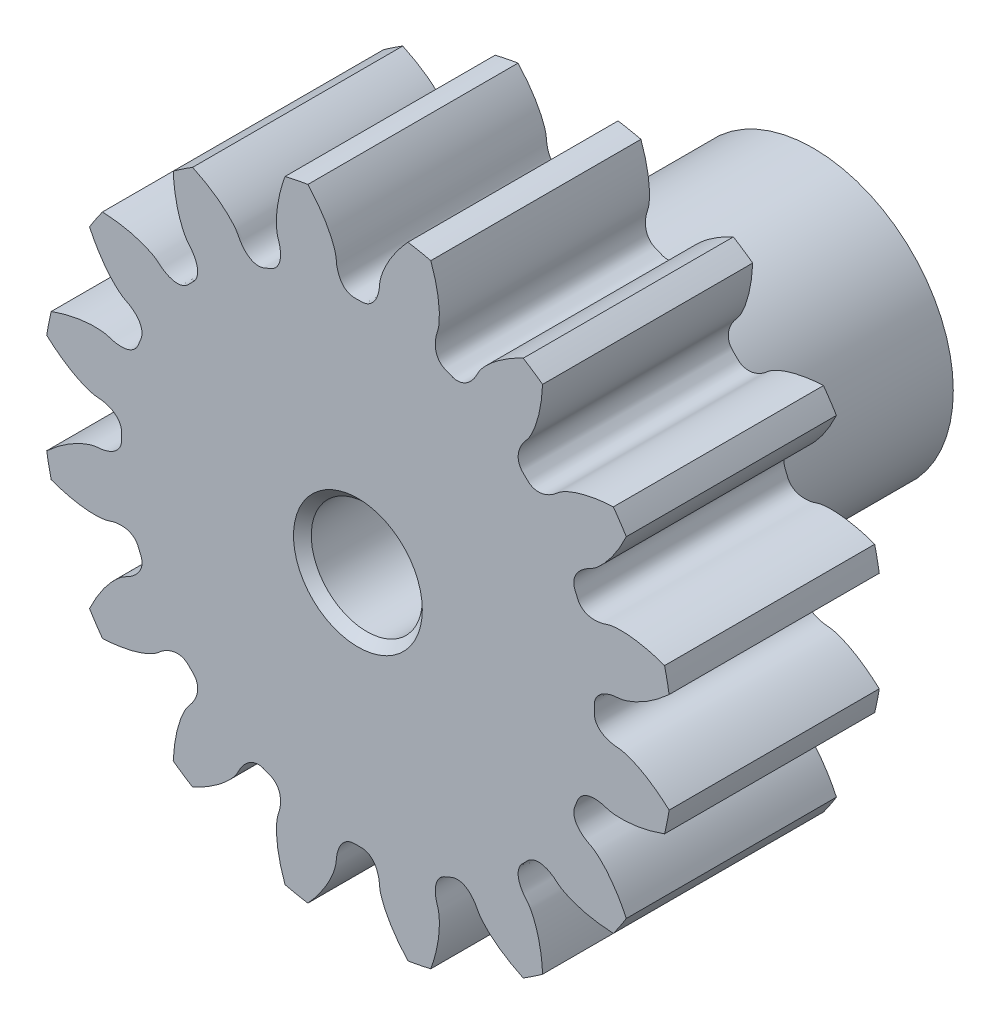
SolidWorks part; units mm, degrees
material "Plain Carbon Steel"
ref_plane "Спереди" through (0, 0, 0) normal (0, 0, 1) x (1, 0, 0)
ref_plane "Сверху" through (0, 0, 0) normal (0, 1, 0) x (1, 0, 0)
ref_plane "Справа" through (0, 0, 0) normal (1, 0, 0) x (0, 0, -1)
ref_axis "Axis1" through (0, 0, 50) along (0, 0, -1)
sketch "SketchRevolveSpur01" plane through (0, 0, 0) normal (1, 0, 0) x (0, 0, -1)
  line L0 (0, 0) -> (1, 0) construction
  line L1 (-3, 0) -> (-3, 9)
  line L2 (-3, 9) -> (3, 9)
  line L3 (3, 9) -> (3, 0)
  line L4 (3, 0) -> (-3, 0)
revolve "Spur01" add sketch "SketchRevolveSpur01" angle 360 about L0
sketch "SketchToothSpur01" plane through (0, 0, 0) normal (0, 0, 1) x (1, 0, 0)
  arc A0 (8.93, 1.469) -> (8.93, -1.469) centre (0, 0) cw
  spline S0 degree 3 poles (8.93, -1.469) (8.852, -1.3959) (8.7347, -1.2926) (8.5758, -1.1667) (8.4638, -1.0839) (8.356, -1.0096) (8.2529, -0.9435) (8.1549, -0.8853) (8.0624, -0.8344) (7.9758, -0.7905) (7.8955, -0.7531) (7.8216, -0.7216) (7.7547, -0.6957) (7.6949, -0.6749) (7.6425, -0.6585) (7.5977, -0.6462) (7.5608, -0.6373) (7.4657, -0.6175) (7.363, -0.618) (7.2566, -0.5967) (7.2079, -0.5852) (7.1608, -0.5717) (7.1154, -0.5561) (7.0716, -0.5383) (7.0293, -0.5181) (6.9883, -0.4951) (6.9488, -0.4691) (6.9107, -0.4393) (6.8743, -0.4052) (6.8401, -0.3659) (6.809, -0.3209) (6.7825, -0.2695) (6.7623, -0.2121) (6.7519, -0.1552) (6.7476, -0.084) (6.7516, 0) (6.7476, 0.084) (6.7519, 0.1552) (6.7623, 0.2121) (6.7825, 0.2695) (6.809, 0.3209) (6.8401, 0.3659) (6.8743, 0.4052) (6.9107, 0.4393) (6.9488, 0.4691) (6.9883, 0.4951) (7.0293, 0.5181) (7.0716, 0.5383) (7.1154, 0.5561) (7.1608, 0.5717) (7.2079, 0.5852) (7.2566, 0.5967) (7.363, 0.618) (7.4657, 0.6175) (7.5608, 0.6373) (7.5977, 0.6462) (7.6425, 0.6585) (7.6949, 0.6749) (7.7547, 0.6957) (7.8216, 0.7216) (7.8955, 0.7531) (7.9758, 0.7905) (8.0624, 0.8344) (8.1549, 0.8853) (8.2529, 0.9435) (8.356, 1.0096) (8.4638, 1.0839) (8.5758, 1.1667) (8.7347, 1.2926) (8.852, 1.3959) (8.93, 1.469) knots 0 0 0 0 0.057365 0.083783 0.108691 0.13209 0.153979 0.174358 0.193228 0.210589 0.22644 0.240781 0.253612 0.264934 0.274747 0.283049 0.289843 0.295126 0.335124 0.344314 0.353262 0.361998 0.370561 0.378997 0.38736 0.395718 0.40415 0.412749 0.42162 0.430875 0.440614 0.450911 0.461775 0.473125 0.48184 0.5 0.51816 0.526875 0.538225 0.549089 0.559386 0.569125 0.57838 0.587251 0.59585 0.604282 0.61264 0.621003 0.629439 0.638002 0.646738 0.655686 0.664876 0.704874 0.710157 0.716951 0.725253 0.735066 0.746388 0.759219 0.77356 0.789411 0.806772 0.825642 0.846021 0.86791 0.891309 0.916217 0.942635 1 1 1 1
extrude "ToothExtrudeCutSpur01" cut sketch "SketchToothSpur01" against normal blind 3 and the other way blind 3
ref_axis "Axis2" through (80.9, 0, 0) along (-1, 0, 0)
ref_plane "Plane1" through (0, 0, 0) normal (0, 0, -1) x (1, 0, 0)
pattern_circular "PatternSpur01" count 16 every 22.5 about axis through (0, 0, 50) along (0, 0, -1) of "ToothExtrudeCutSpur01"
sketch "HubSketchSide1" plane through (0, 0, 0) normal (1, 0, 0) x (0, 0, -1)
  line L0 (0, 0) -> (1, 0) construction
  line L1 (3, 4) -> (10, 4)
  line L2 (10, 4) -> (10, 0)
  line L3 (10, 0) -> (3, 0)
  line L4 (3, 0) -> (3, 4)
  dimension "HubRadius1" = 4
revolve "HubRevolve1" add sketch "HubSketchSide1" angle 360 about L0
sketch "BoreRevolveSketch" plane through (0, 0, 0) normal (1, 0, 0) x (0, 0, -1)
  line L0 (0, 0) -> (1, 0) construction
  line L1 (-3, 0) -> (10, 0)
  line L2 (10, 0) -> (10, 1.839)
  line L3 (10, 1.839) -> (9.746, 1.585)
  line L4 (9.746, 1.585) -> (-2.746, 1.585)
  line L5 (-2.746, 1.585) -> (-3, 1.839)
  line L6 (-3, 1.839) -> (-3, 0)
  dimension "TaperSide1" = 1.839
  dimension "Chamfer1X" = 0.254
  dimension "Chamfer1Y" = 0.254
  dimension "TaperSide2" = 1.839
revolve "BoreRevolveCut" cut sketch "BoreRevolveSketch" angle 360 about L0
sketch "AuxiliarySketchSpur01" plane through (0, 0, 0) normal (0, 0, 1) x (1, 0, 0)
  circle A0 centre (0, 0) radius 8 construction
  circle A1 centre (0, 0) radius 7.5175 construction
  circle A2 centre (0, 0) radius 7.5253 construction
  circle A3 centre (0, 0) radius 9 construction
  circle A4 centre (0, 0) radius 6.75 construction
  dimension "PitchDiameter" = 16
  dimension "BaseDiameter" = 15.0351
  dimension "FormDiameter" = 15.0506
  dimension "MajorDiameter" = 18
  dimension "MinorDiameter" = 13.5
